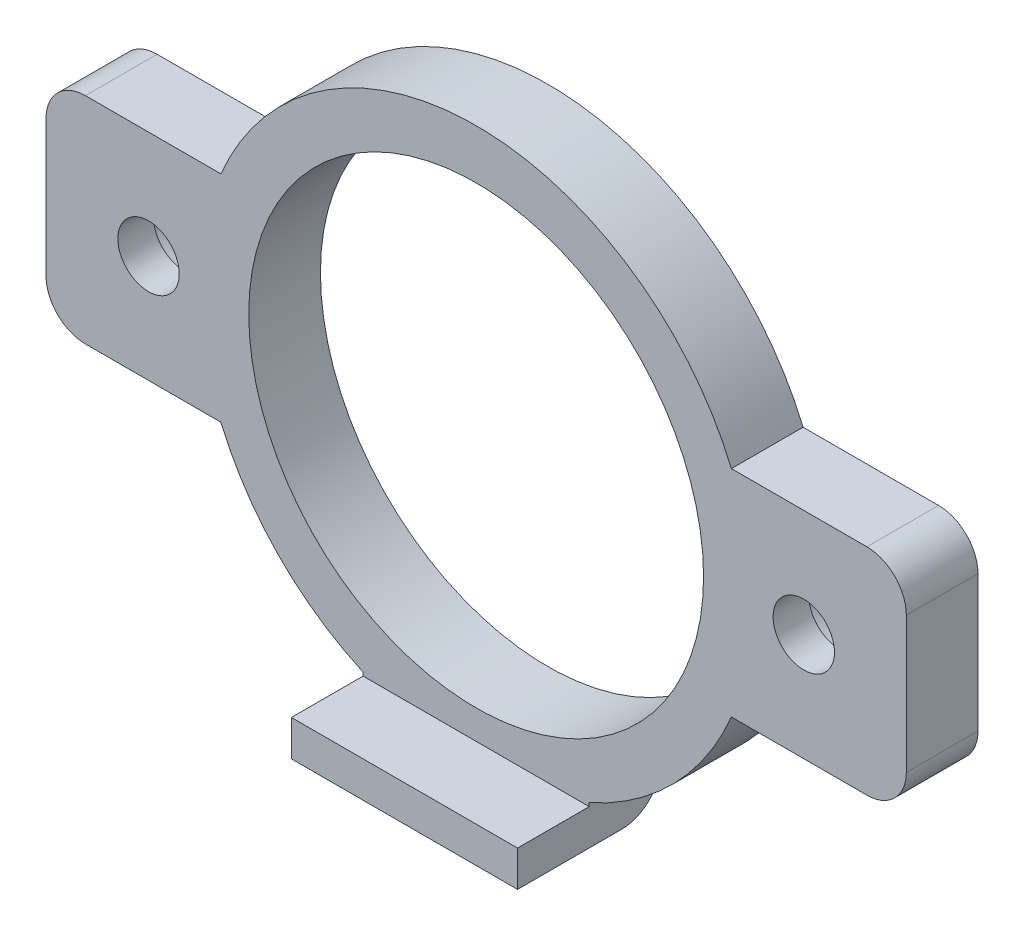
SolidWorks part; units mm, degrees
ref_plane "前视基准面" through (0, 0, 0) normal (0, 0, 1) x (1, 0, 0)
ref_plane "上视基准面" through (0, 0, 0) normal (0, 1, 0) x (1, 0, 0)
ref_plane "右视基准面" through (0, 0, 0) normal (1, 0, 0) x (0, 0, -1)
sketch "草图1" plane through (0, 0, 0) normal (0, 0, 1) x (1, 0, 0)
  line L9 (3.1544, -7.15) -> (3.1544, -8.15)
  line L12 (3.1544, -7.15) -> (-3.1544, -7.15)
  line L17 (12, 3) -> (7.1207, 3)
  line L18 (12, 3) -> (12, -3)
  line L19 (12, -3) -> (7.1207, -3)
  line L23 (3.1544, -8.15) -> (-3.1544, -8.15)
  line L24 (-3.1544, -8.15) -> (-3.1544, -7.15)
  line L25 (3.1544, -7.15) -> (-3.1544, -7.15)
  line L26 (0, 0) -> (0, -3.5928)
  line L27 (-12, -3) -> (-7.1207, -3)
  line L28 (3.1544, -7.0536) -> (3.1544, -7.15)
  line L29 (-12, 3) -> (-12, -3)
  line L30 (-12, 3) -> (-7.1207, 3)
  line L31 (-3.1544, -7.0536) -> (-3.1544, -7.15)
  circle A3 centre (-9.14, 0) radius 0.8559
  circle A4 centre (-9.14, 0) radius 1.5105
  circle A11 centre (0, 0) radius 6.3441
  circle A12 centre (9.14, 0) radius 1.5105
  circle A13 centre (9.14, 0) radius 0.8559
  arc A16 (7.1207, 3) -> (-7.1207, 3) centre (0, 0) ccw
  arc A17 (3.1544, -7.0536) -> (7.1207, -3) centre (0, 0) ccw
  arc A18 (-7.1207, -3) -> (-3.1544, -7.0536) centre (0, 0) ccw
  point P21 (12, 0)
  dimension "D2" = 12
extrude "凸台-拉伸2" add sketch "草图1" along normal blind 2 contours A11 | L28 A17 L19 L18 L17 A16 L30 L29 L27 A18 L31 L12
extrude "凸台-拉伸3" add sketch "草图1<7>" along normal blind 4 contours L9 L23 L24 L12
sketch "草图1<7>" plane through (0, 0, 0) normal (0, 0, 1) x (1, 0, 0) same geometry as "草图1"
extrude "切除-拉伸3" cut sketch "草图1<8>" along normal blind 3.5 contours A3 | A13
sketch "草图1<8>" plane through (0, 0, 0) normal (0, 0, 1) x (1, 0, 0) same geometry as "草图1"
extrude "切除-拉伸4" cut sketch "草图1<9>" along normal blind 1 contours A12 | A4
sketch "草图1<9>" plane through (0, 0, 0) normal (0, 0, 1) x (1, 0, 0) same geometry as "草图1"
fillet "圆角2" radius 1.1 1 edges at (0, -8.15, 0)
fillet "圆角3" radius 1.1 4 edges at (-12, -3, 1) (-12, 3, 1) (12, -3, 1) (12, 3, 1)
